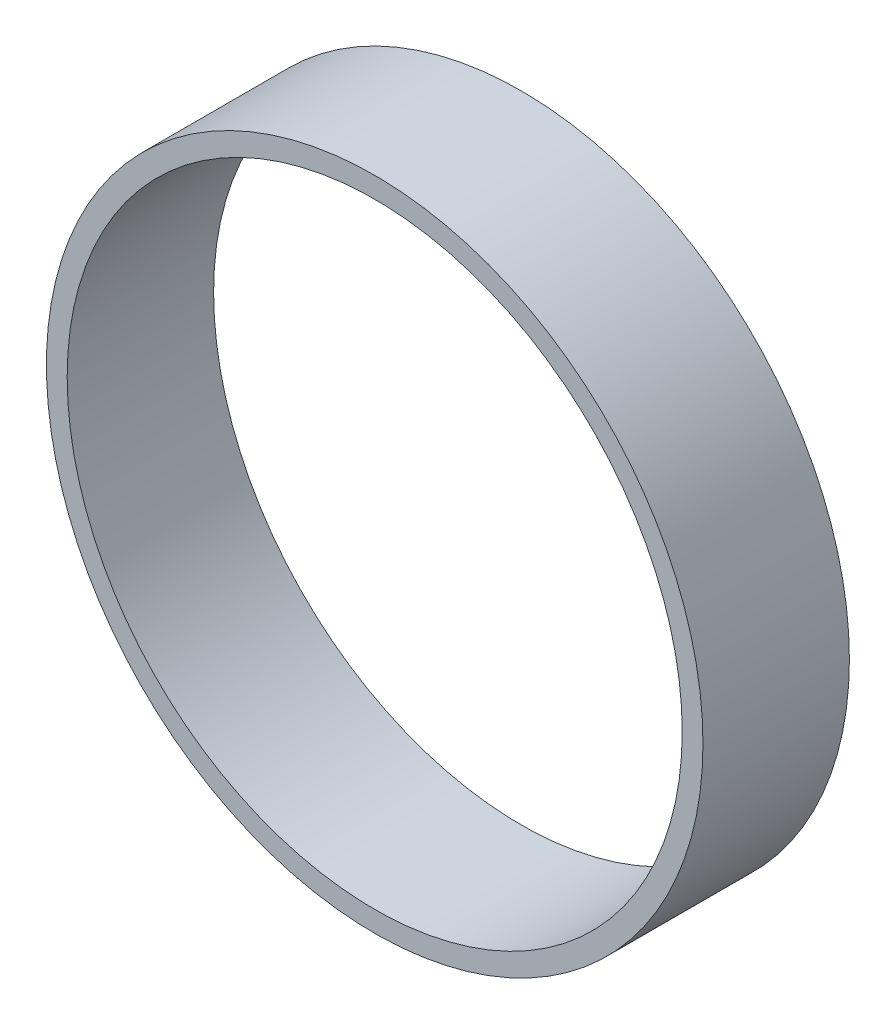
SolidWorks part; units mm, degrees
ref_plane "Front Plane" through (0, 0, 0) normal (0, 0, 1) x (1, 0, 0)
ref_plane "Top Plane" through (0, 0, 0) normal (0, 1, 0) x (1, 0, 0)
ref_plane "Right Plane" through (0, 0, 0) normal (1, 0, 0) x (0, 0, -1)
sketch "Sketch1" plane through (0, 0, 0) normal (0, 0, 1) x (1, 0, 0)
  circle A0 centre (0, 0) radius 53.35
  circle A1 centre (0, 0) radius 56.95
  dimension "Out_dia" = 113.9
  dimension "Thickness" = 3.6
extrude "BasePipe" add sketch "Sketch1" along normal mid plane 25.4
